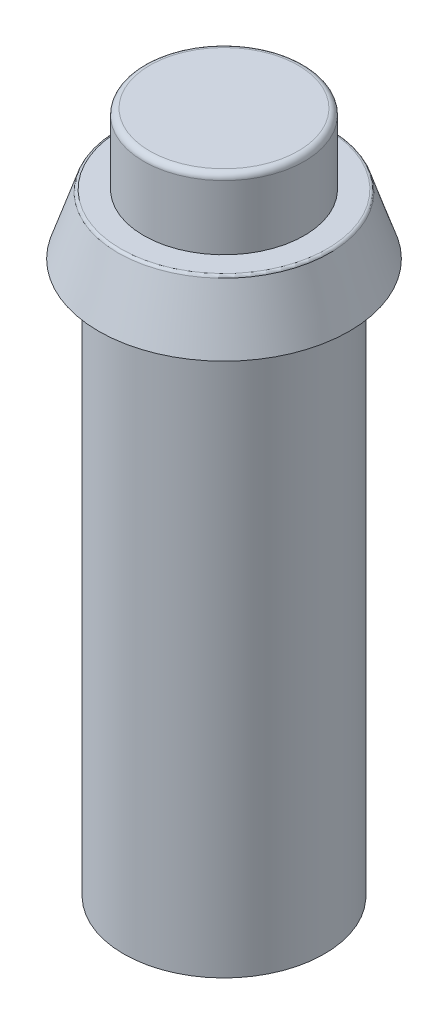
SolidWorks part; units mm, degrees
ref_plane "Front Plane" through (0, 0, 0) normal (0, 0, 1) x (1, 0, 0)
ref_plane "Top Plane" through (0, 0, 0) normal (0, 1, 0) x (1, 0, 0)
ref_plane "Right Plane" through (0, 0, 0) normal (1, 0, 0) x (0, 0, -1)
sketch "Sketch1" plane through (0, 0, 0) normal (0, 1, 0) x (1, 0, 0)
  circle A0 centre (0, 0) radius 5
extrude "Boss-Extrude1" add sketch "Sketch1" along normal blind 27.5
sketch "Sketch2" plane through (0, 27.5, 0) normal (0, 1, 0) x (1, 0, 0)
  circle A0 centre (0, 0) radius 6.25
extrude "Boss-Extrude2" add sketch "Sketch2" along normal blind 3
sketch "Sketch3" plane through (0, 30.5, 0) normal (0, 1, 0) x (1, 0, 0)
  circle A0 centre (0, 0) radius 4
extrude "Boss-Extrude3" add sketch "Sketch3" along normal blind 3.5
chamfer "Chamfer1" distance 3 distance2 1 1 edges at (0, 30.5, 6.25) first distance on face at (0, 30.5, 6.25)
fillet "Fillet1" radius 0.3 1 edges at (0, 34, 4)
fillet "Fillet2" radius 0.15 1 edges at (0, 30.5, 5.25)
